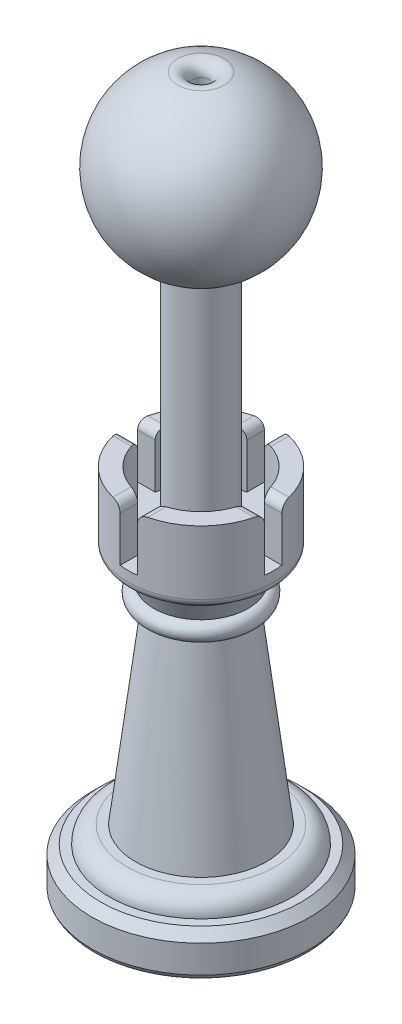
SolidWorks part; units mm, degrees
ref_plane "Front Plane" through (0, 0, 0) normal (0, 0, 1) x (1, 0, 0)
ref_plane "Top Plane" through (0, 0, 0) normal (0, 1, 0) x (1, 0, 0)
ref_plane "Right Plane" through (0, 0, 0) normal (1, 0, 0) x (0, 0, -1)
sketch "Sketch1" plane through (0, 0, 0) normal (0, 0, 1) x (1, 0, 0)
  line L0 (0, 0) -> (0, 31.75)
  line L1 (0, 31.75) -> (-6.35, 31.75)
  line L2 (-6.35, 31.75) -> (-6.35, 25.4)
  line L3 (-6.35, 25.4) -> (-4.826, 25.4)
  line L4 (-4.826, 25.4) -> (-4.826, 24.638)
  line L5 (-4.826, 24.638) -> (-4.1128, 23.0632)
  line L8 (-4.1128, 21.5392) -> (-3.683, 21.5392)
  line L9 (-3.683, 21.5392) -> (-5.715, 4.699)
  line L10 (-5.715, 4.699) -> (-8.001, 4.699)
  line L11 (-8.001, 4.699) -> (-8.001, 3.175)
  line L12 (-8.001, 3.175) -> (-9.525, 3.175)
  line L13 (-9.525, 3.175) -> (-9.525, 0)
  line L14 (-9.525, 0) -> (0, 0)
  arc A0 (-4.1128, 23.0632) -> (-4.1128, 21.5392) centre (-4.1128, 22.3012) ccw
  dimension "D11" = 0.4298
  dimension "D1" = 31.75
  dimension "D2" = 9.525
  dimension "D3" = 3.175
  dimension "D4" = 1.524
  dimension "D5" = 1.524
  dimension "D6" = 21.5392
  dimension "D7" = 6.35
  dimension "D8" = 6.35
  dimension "D9" = 1.524
  dimension "D10" = 1.524
  dimension "D12" = 0.762
  dimension "D13" = 3.683
  dimension "D15" = 2.286
revolve "Revolve1" add sketch "Sketch1" angle 360 about L0
chamfer "Chamfer1" distance 0.762 angle 45 1 edges at (0, 3.175, -9.525)
fillet "Fillet1" radius 0.762 2 edges at (0, 25.4, -4.826) (0, 25.4, -6.35)
sketch "Sketch2" plane through (0, 31.75, 0) normal (0, 1, 0) x (1, 0, 0)
  line L1 (-13.8131, 0.762) -> (13.8131, 0.762)
  line L2 (-13.8131, 0.762) -> (-13.8131, -0.762)
  line L3 (-13.8131, -0.762) -> (13.8131, -0.762)
  line L4 (13.8131, 0.762) -> (13.8131, -0.762)
  line L5 (-13.8131, 0.762) -> (13.8131, -0.762) construction
  line L6 (-13.8131, -0.762) -> (13.8131, 0.762) construction
  line L7 (-0.762, 10.4631) -> (0.762, 10.4631)
  line L8 (-0.762, 10.4631) -> (-0.762, -10.4631)
  line L9 (-0.762, -10.4631) -> (0.762, -10.4631)
  line L10 (0.762, 10.4631) -> (0.762, -10.4631)
  line L11 (-0.762, 10.4631) -> (0.762, -10.4631) construction
  line L12 (-0.762, -10.4631) -> (0.762, 10.4631) construction
  circle A0 centre (0, 0) radius 4.826
  circle A1 centre (0, 0) radius 6.35 construction
  circle M6 centre (0, 0) radius 6.35
  dimension "D1" = 1.524
  dimension "D2" = 1.524
  dimension "D3" = 1.524
extrude "Cut-Extrude4" cut sketch "Sketch2" against normal blind 4.699 contours L1 A0 L10 | L8 A0 L1 | L3 A0 L8 | L10 A0 L3 | A0 L1 L3 M6 | A0 L10 L8 M6 | A0 L3 L1 M6 | A0 L8 L10 M6 | L8 A0 L10 L3 | L10 L1 L8 L3 | L1 A0 L3 L8 | L10 A0 L8 L1 | L3 A0 L1 L10 region at (-5.5703, 31.75, 0) region at (-2.3808, 31.75, -2.3808) region at (-2.784, 31.75, 0) region at (0, 31.75, -5.5703) region at (0, 31.75, -2.784) region at (0, 31.75, 0) region at (-2.3808, 31.75, 2.3808) region at (0, 31.75, 5.5703) region at (2.3808, 31.75, -2.3808) region at (2.784, 31.75, 0) region at (0, 31.75, 2.784) region at (5.5703, 31.75, 0) region at (2.3808, 31.75, 2.3808)
fillet "Fillet2" radius 0.762 8 edges at (-0.762, 31.75, 5.5348) (0.762, 31.75, 5.5348) (5.5348, 31.75, 0.762) (5.5348, 31.75, -0.762) (0.762, 31.75, -5.5348) (-0.762, 31.75, -5.5348) (-5.5348, 31.75, -0.762) (-5.5348, 31.75, 0.762)
fillet "Fillet3" radius 1.524 1 edges at (0, 4.699, -8.001)
sketch "Sketch3" plane through (0, 3.175, 0) normal (0, 1, 0) x (1, 0, 0)
  point P0 (0, 0)
sketch "Sketch4" plane through (0, 0, 0) normal (0, -1, 0) x (1, 0, 0)
  circle A0 centre (0, 0) radius 9.525 construction
  point P0 (0, 0)
  point P1 (9.525, 0)
ref_plane "Plane1" through (0, 0, 0) normal (0, 0, 1) x (1, 0, 0)
sketch "Sketch5" plane through (0, 0, 0) normal (0, 0, 1) x (1, 0, 0)
  line L0 (0, 0) -> (-10, 0)
  line L1 (-10, 0) -> (-5.37, -2.68)
  line L2 (-5.37, -2.68) -> (0, -2.68)
  line L3 (0, -2.68) -> (0, 0)
  line L4 (0, 24.638) -> (0, 61.8911) construction
  line L5 (4.826, 24.638) -> (-4.826, 24.638) construction
  line L7 (0, 24.638) -> (-2.5, 24.638)
  line L8 (0, 24.638) -> (0, 47.32)
  line L9 (0, 47.32) -> (-2.5, 47.32)
  line L10 (-2.5, 24.638) -> (-2.5, 47.32)
  circle A0 centre (0, 54.3911) radius 7.5
  dimension "D6" = 15
  dimension "D1" = 2.68
  dimension "D2" = 5.37
  dimension "D3" = 10
  dimension "D4" = 2.5
  dimension "D5" = 50
revolve "Revolve3" add sketch "Sketch5" angle 360 about L4 region at (-3.9587, -1.2054, 0) region at (-3.2015, 54.4505, 0) region at (-0.9412, 47.148, 0)
sketch "Sketch6" plane through (0, -2.68, 0) normal (0, -1, 0) x (1, 0, 0)
  circle A0 centre (0, 0) radius 0.75
  dimension "D1" = 1.5
extrude "Cut-Extrude5" cut sketch "Sketch6" against normal blind 65
sketch "Sketch7" plane through (0, -2.68, 0) normal (0, -1, 0) x (1, 0, 0)
  circle A0 centre (0, 0) radius 5.1
  dimension "D1" = 10.2
extrude "Cut-Extrude6" cut sketch "Sketch7" against normal blind 4
fillet "Fillet4" radius 1 3 edges at (0, 61.8535, -0.75) (0, 0, -10) (0, -2.68, -5.1)
